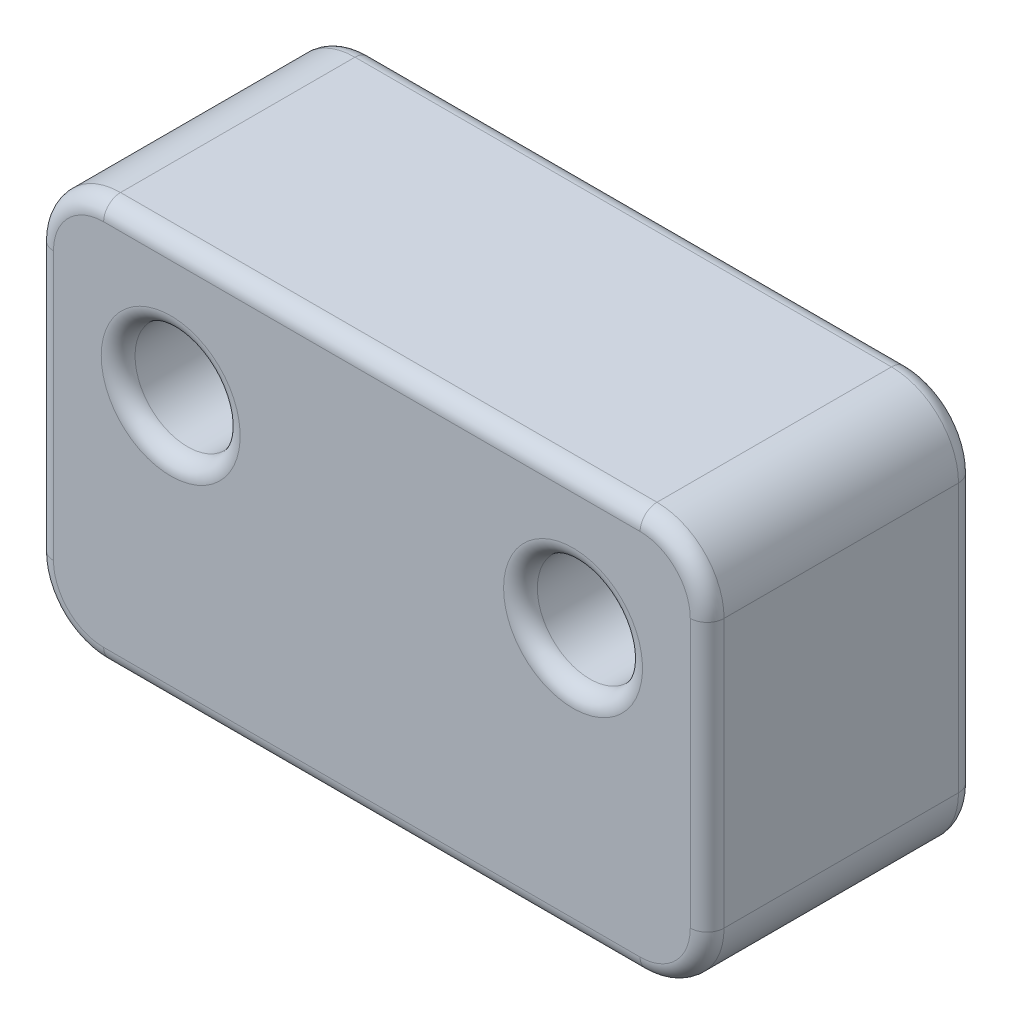
SolidWorks part; units mm, degrees
material "Nylon 101"
ref_plane "Front Plane" through (0, 0, 0) normal (0, 0, 1) x (1, 0, 0)
ref_plane "Top Plane" through (0, 0, 0) normal (0, 1, 0) x (1, 0, 0)
ref_plane "Right Plane" through (0, 0, 0) normal (1, 0, 0) x (0, 0, -1)
sketch "Sketch1" plane through (0, 0, 0) normal (0, 0, 1) x (1, 0, 0)
  line L0 (6.35, 12.7) -> (25.4, 12.7) construction
  line L1 (0, 0) -> (31.75, 0)
  line L2 (0, 0) -> (0, 19.05)
  line L3 (0, 19.05) -> (31.75, 19.05)
  line L4 (31.75, 0) -> (31.75, 19.05)
  circle A0 centre (6.35, 12.7) radius 2.4892
  circle A1 centre (25.4, 12.7) radius 2.4892
  point P9 (6.9755, 12.7)
  point P10 (15.875, 12.7)
  point P11 (15.875, 19.05)
  point P12 (22.5902, 12.7)
  dimension "D3" = 4.9784
  dimension "D1" = 31.75
  dimension "D2" = 19.05
  dimension "D4" = 6.35
  dimension "D5" = 19.05
extrude "Boss-Extrude1" add sketch "Sketch1" along normal mid plane 12.7
fillet "Fillet1" radius 3.175 4 edges at (31.75, 19.05, 0) (31.75, 0, 0) (0, 0, 0) (0, 19.05, 0)
fillet "Fillet2" radius 0.8 20 edges at (27.8892, 12.7, -6.35) (27.8892, 12.7, 6.35) (8.8392, 12.7, -6.35) (8.8392, 12.7, 6.35) (15.875, 0, -6.35) (31.75, 9.525, -6.35) (15.875, 19.05, -6.35) (0, 9.525, 6.35) (15.875, 0, 6.35) (31.75, 9.525, 6.35) (0.9299, 18.1201, -6.35) (0.9299, 0.9299, -6.35) (30.8201, 0.9299, -6.35) (30.8201, 18.1201, -6.35) (0.9299, 18.1201, 6.35) (0.9299, 0.9299, 6.35) (30.8201, 0.9299, 6.35) (30.8201, 18.1201, 6.35) (0, 9.525, -6.35) (15.875, 19.05, 6.35)
